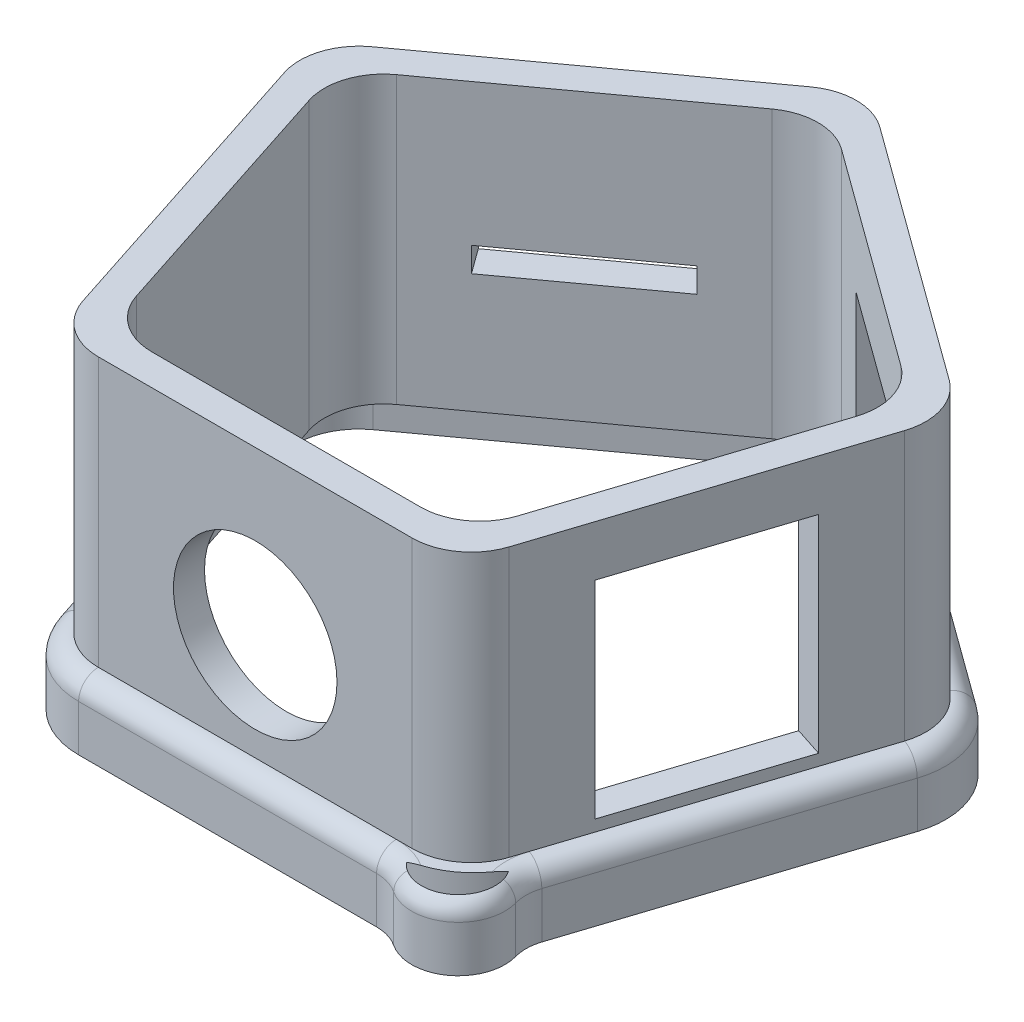
SolidWorks part; units mm, degrees
material "ABS"
ref_plane "Front Plane" through (0, 0, 0) normal (0, 0, 1) x (1, 0, 0)
ref_plane "Top Plane" through (0, 0, 0) normal (0, 1, 0) x (1, 0, 0)
ref_plane "Right Plane" through (0, 0, 0) normal (1, 0, 0) x (0, 0, -1)
sketch "Sketch1" plane through (0, 0, 0) normal (0, 0, 1) x (1, 0, 0)
  line L1 (-22.86, -15.875) -> (22.86, -15.875)
  line L2 (-22.86, -15.875) -> (-22.86, 15.875)
  line L3 (-22.86, 15.875) -> (22.86, 15.875)
  line L4 (22.86, -15.875) -> (22.86, 15.875)
  line L5 (-22.86, -15.875) -> (22.86, 15.875) construction
  line L6 (-22.86, 15.875) -> (22.86, -15.875) construction
  circle A0 centre (0, 0) radius 10.16
  dimension "D1" = 20.32
  dimension "D2" = 45.72
  dimension "D3" = 31.75
extrude "Boss-Extrude1" add sketch "Sketch1" along normal blind 4
sketch "Sketch2" plane through (0, 15.875, 0) normal (0, 1, 0) x (1, 0, 0)
  line L0 (22.86, 0) -> (36.9883, 43.4823)
  line L1 (36.9883, 43.4823) -> (0, 70.3558)
  line L2 (0, 70.3558) -> (-36.9883, 43.4823)
  line L3 (-36.9883, 43.4823) -> (-22.86, 0)
  line L4 (-22.86, 0) -> (22.86, 0)
  line L6 (-41.6905, 45.0102) -> (-25.7662, -4)
  line L7 (-25.7662, -4) -> (25.7662, -4)
  line L8 (25.7662, -4) -> (41.6905, 45.0102)
  line L9 (41.6905, 45.0102) -> (0, 75.3001)
  line L10 (0, 75.3001) -> (-41.6905, 45.0102)
  line L11 (-22.86, 0) -> (-22.86, -4)
  line L12 (-22.86, -4) -> (22.86, 0)
  line L13 (22.86, -4) -> (22.86, 0)
  line M7 (-22.86, 0) -> (-22.86, -4)
  line M9 (22.86, -4) -> (22.86, 0)
  dimension "D1" = 108
  dimension "D2" = 108
  dimension "D3" = 4
extrude "Boss-Extrude2" add sketch "Sketch2" against normal up to surface (31.75 mm away) contours L9 L10 L6 L7 L3 L2 L1 L0 L8 M7 M9 up to face at (0, -15.875, 2)
sketch "Sketch3" plane through (0, 0, 4) normal (0, 0, 1) x (1, 0, 0)
  circle A0 centre (0, 0) radius 10.033
  dimension "D1" = 20.066
extrude "Cut-Extrude1" [suppressed] cut sketch "Sketch3" against normal blind 11.62
sketch "Sketch4" plane through (0, 15.875, 0) normal (0, 1, 0) x (1, 0, 0)
  line L0 (0, 70.3558) -> (0, 0)
  line L1 (22.86, 0) -> (-22.86, 0) construction
  line L2 (36.9883, 43.4823) -> (-29.9241, 21.7412)
  line L3 (-36.9883, 43.4823) -> (-22.86, 0) construction
sketch "Sketch5" plane through (0, 0, 0) normal (1, 0, 0) x (0, 0, -1)
  line L0 (43.4823, 15.875) -> (21.7412, 15.875) construction
  line L1 (43.4823, 15.875) -> (21.7412, 15.875)
  line L2 (31.5133, 15.875) -> (31.5133, 7.2346)
pattern_circular "CirPattern1" [suppressed] count 5 over 360 about axis through (0, 15.875, -31.5133) along (0, -1, 0)
fillet "Fillet1" radius 7.62 10 edges at (-22.86, 0, 0) (-36.9883, 0, -43.4823) (0, 0, -70.3558) (36.9883, 0, -43.4823) (22.86, 0, 0) (25.7662, 0, 4) (41.6905, 0, -45.0102) (0, 0, -75.3001) (-41.6905, 0, -45.0102) (-25.7662, 0, 4)
sketch "Sketch6" plane through (0, 15.875, 0) normal (0, 1, 0) x (1, 0, 0)
  line L0 (24.5708, 5.2653) -> (35.2775, 38.217) construction
  line L1 (17.3237, 0) -> (-17.3237, 0) construction
  line L2 (-35.2775, 38.217) -> (-24.5708, 5.2653) construction
  line L3 (-4.4789, 67.1017) -> (-32.5093, 46.7364) construction
  line L4 (32.5093, 46.7364) -> (4.4789, 67.1017) construction
  line L5 (-20.2299, -4) -> (20.2299, -4)
  line L6 (27.477, 1.2653) -> (39.9797, 39.7449)
  line L7 (37.2116, 48.2643) -> (4.4789, 72.046)
  line L8 (-4.4789, 72.046) -> (-37.2116, 48.2643)
  line L9 (-39.9797, 39.7449) -> (-27.477, 1.2653)
  line L10 (-20.2299, -4) -> (20.2299, -4)
  line L11 (27.477, 1.2653) -> (39.9797, 39.7449)
  line L12 (37.2116, 48.2643) -> (4.4789, 72.046)
  line L13 (-4.4789, 72.046) -> (-37.2116, 48.2643)
  line L14 (-39.9797, 39.7449) -> (-27.477, 1.2653)
  line L15 (24.5708, 5.2653) -> (35.2775, 38.217)
  line L16 (17.3237, 0) -> (-17.3237, 0)
  line L17 (-35.2775, 38.217) -> (-24.5708, 5.2653)
  line L18 (-4.4789, 67.1017) -> (-32.5093, 46.7364)
  line L19 (32.5093, 46.7364) -> (4.4789, 67.1017)
  arc A0 (35.2775, 38.217) -> (32.5093, 46.7364) centre (28.0304, 40.5717) ccw construction
  arc A1 (17.3237, 0) -> (24.5708, 5.2653) centre (17.3237, 7.62) ccw construction
  arc A2 (-24.5708, 5.2653) -> (-17.3237, 0) centre (-17.3237, 7.62) ccw construction
  arc A3 (-32.5093, 46.7364) -> (-35.2775, 38.217) centre (-28.0304, 40.5717) ccw construction
  arc A4 (4.4789, 67.1017) -> (-4.4789, 67.1017) centre (0, 60.937) ccw construction
  arc A5 (20.2299, -4) -> (27.477, 1.2653) centre (20.2299, 3.62) ccw
  arc A6 (39.9797, 39.7449) -> (37.2116, 48.2643) centre (32.7327, 42.0996) ccw
  arc A7 (4.4789, 72.046) -> (-4.4789, 72.046) centre (0, 65.8813) ccw
  arc A8 (-37.2116, 48.2643) -> (-39.9797, 39.7449) centre (-32.7327, 42.0996) ccw
  arc A9 (-27.477, 1.2653) -> (-20.2299, -4) centre (-20.2299, 3.62) ccw
  arc A10 (20.2299, -4) -> (27.477, 1.2653) centre (20.2299, 3.62) ccw
  arc A11 (39.9797, 39.7449) -> (37.2116, 48.2643) centre (32.7327, 42.0996) ccw
  arc A12 (4.4789, 72.046) -> (-4.4789, 72.046) centre (0, 65.8813) ccw
  arc A13 (-37.2116, 48.2643) -> (-39.9797, 39.7449) centre (-32.7327, 42.0996) ccw
  arc A14 (-27.477, 1.2653) -> (-20.2299, -4) centre (-20.2299, 3.62) ccw
  arc A15 (35.2775, 38.217) -> (32.5093, 46.7364) centre (28.0304, 40.5717) ccw
  arc A16 (17.3237, 0) -> (24.5708, 5.2653) centre (17.3237, 7.62) ccw
  arc A17 (-24.5708, 5.2653) -> (-17.3237, 0) centre (-17.3237, 7.62) ccw
  arc A18 (-32.5093, 46.7364) -> (-35.2775, 38.217) centre (-28.0304, 40.5717) ccw
  arc A19 (4.4789, 67.1017) -> (-4.4789, 67.1017) centre (0, 60.937) ccw
  dimension "D1" = 0
extrude "Boss-Extrude3" add sketch "Sketch6" along normal blind 5.08
sketch "Sketch7" plane through (-35.8073, 0, -49.2846) normal (-0.5878, 0, -0.809) x (-0.809, 0, 0.5878)
  line L0 (-18.4941, 20.955) -> (-18.4941, 17.145)
  line L1 (-38.724, 20.955) -> (1.7358, 20.955) construction
  circle A0 centre (-18.4941, 17.145) radius 2.5
  dimension "D1" = 5
  dimension "D2" = 3.81
sketch "Sketch8" plane through (0, -15.875, 0) normal (0, -1, 0) x (1, 0, 0)
  line L0 (-27.477, -1.2653) -> (-39.9797, -39.7449) construction
  line L1 (-27.477, -1.2653) -> (-39.9797, -39.7449)
  line L7 (39.9797, -39.7449) -> (27.477, -1.2653)
  line L8 (20.2299, 4) -> (-20.2299, 4)
  line L9 (-27.477, -1.2653) -> (-39.9797, -39.7449)
  line L10 (-37.2116, -48.2643) -> (-4.4789, -72.046)
  line L11 (4.4789, -72.046) -> (37.2116, -48.2643)
  line L12 (39.9797, -39.7449) -> (27.477, -1.2653)
  line L13 (20.2299, 4) -> (-20.2299, 4)
  line L14 (-27.477, -1.2653) -> (-39.9797, -39.7449)
  line L15 (-37.2116, -48.2643) -> (-4.4789, -72.046)
  line L16 (4.4789, -72.046) -> (37.2116, -48.2643)
  line L22 (42.3954, -38.96) -> (29.8927, -0.4804)
  line L23 (20.2299, 6.54) -> (-20.2299, 6.54)
  line L24 (-29.8927, -0.4804) -> (-42.3954, -38.96)
  line L25 (-38.7046, -50.3192) -> (-5.9719, -74.1009)
  line L26 (5.9719, -74.1009) -> (38.7046, -50.3192)
  line L27 (42.3954, -38.96) -> (29.8927, -0.4804)
  line L28 (20.2299, 6.54) -> (-20.2299, 6.54)
  line L29 (-29.8927, -0.4804) -> (-42.3954, -38.96)
  line L30 (-38.7046, -50.3192) -> (-5.9719, -74.1009)
  line L31 (5.9719, -74.1009) -> (38.7046, -50.3192)
  arc A5 (27.477, -1.2653) -> (20.2299, 4) centre (20.2299, -3.62) ccw
  arc A6 (-20.2299, 4) -> (-27.477, -1.2653) centre (-20.2299, -3.62) ccw
  arc A7 (-39.9797, -39.7449) -> (-37.2116, -48.2643) centre (-32.7327, -42.0996) ccw
  arc A8 (-4.4789, -72.046) -> (4.4789, -72.046) centre (0, -65.8813) ccw
  arc A9 (37.2116, -48.2643) -> (39.9797, -39.7449) centre (32.7327, -42.0996) ccw
  arc A10 (27.477, -1.2653) -> (20.2299, 4) centre (20.2299, -3.62) ccw
  arc A11 (-20.2299, 4) -> (-27.477, -1.2653) centre (-20.2299, -3.62) ccw
  arc A12 (-39.9797, -39.7449) -> (-37.2116, -48.2643) centre (-32.7327, -42.0996) ccw
  arc A13 (-4.4789, -72.046) -> (4.4789, -72.046) centre (0, -65.8813) ccw
  arc A14 (37.2116, -48.2643) -> (39.9797, -39.7449) centre (32.7327, -42.0996) ccw
  arc A20 (29.8927, -0.4804) -> (20.2299, 6.54) centre (20.2299, -3.62) ccw
  arc A21 (-20.2299, 6.54) -> (-29.8927, -0.4804) centre (-20.2299, -3.62) ccw
  arc A22 (-42.3954, -38.96) -> (-38.7046, -50.3192) centre (-32.7327, -42.0996) ccw
  arc A23 (-5.9719, -74.1009) -> (5.9719, -74.1009) centre (0, -65.8813) ccw
  arc A24 (38.7046, -50.3192) -> (42.3954, -38.96) centre (32.7327, -42.0996) ccw
  arc A25 (29.8927, -0.4804) -> (20.2299, 6.54) centre (20.2299, -3.62) ccw
  arc A26 (-20.2299, 6.54) -> (-29.8927, -0.4804) centre (-20.2299, -3.62) ccw
  arc A27 (-42.3954, -38.96) -> (-38.7046, -50.3192) centre (-32.7327, -42.0996) ccw
  arc A28 (-5.9719, -74.1009) -> (5.9719, -74.1009) centre (0, -65.8813) ccw
  arc A29 (38.7046, -50.3192) -> (42.3954, -38.96) centre (32.7327, -42.0996) ccw
  line M31 (39.9797, -39.7449) -> (27.477, -1.2653)
  arc M32 (27.477, -1.2653) -> (20.2299, 4) centre (20.2299, -3.62) ccw
  line M33 (20.2299, 4) -> (-20.2299, 4)
  arc M34 (-20.2299, 4) -> (-27.477, -1.2653) centre (-20.2299, -3.62) ccw
  line M35 (-27.477, -1.2653) -> (-39.9797, -39.7449)
  arc M36 (-39.9797, -39.7449) -> (-37.2116, -48.2643) centre (-32.7327, -42.0996) ccw
  line M37 (-37.2116, -48.2643) -> (-4.4789, -72.046)
  arc M38 (-4.4789, -72.046) -> (4.4789, -72.046) centre (0, -65.8813) ccw
  line M39 (4.4789, -72.046) -> (37.2116, -48.2643)
  arc M40 (37.2116, -48.2643) -> (39.9797, -39.7449) centre (32.7327, -42.0996) ccw
  dimension "D1" = 0
  dimension "D2" = 2.54
extrude "Boss-Extrude4" add sketch "Sketch8" along normal blind 6.35 and the other way blind 2.159 contours L31 A29 L27 A25 L28 A26 L29 A27 L30 A28 M31 M40 M39 M38 M37 M36 M35 M34 M33 M32
sketch "Sketch9" plane through (-37.3003, 0, -51.3395) normal (-0.5878, 0, -0.809) x (-0.809, 0, 0.5878)
  line L0 (1.7358, -15.875) -> (-38.724, -15.875) construction
  line L1 (1.7358, -15.875) -> (-38.724, -15.875)
  line L2 (-18.4941, -15.875) -> (-18.4941, -19.685)
  circle A0 centre (-18.4941, -19.685) radius 1.7
  dimension "D2" = 3.4
  dimension "D1" = 3.81
sketch "Sketch11" plane through (0, -22.225, 0) normal (0, -1, 0) x (1, 0, 0)
  line L0 (20.2299, 6.54) -> (19.9488, 5.4149)
  line L1 (19.9488, 5.4149) -> (27.19, 1.5678)
  line L2 (27.19, 1.5678) -> (29.8927, -0.4804)
  line L5 (5.9719, -74.1009) -> (38.7046, -50.3192)
  line L6 (42.3954, -38.96) -> (29.8927, -0.4804)
  line L7 (20.2299, 6.54) -> (-20.2299, 6.54)
  line L8 (-29.8927, -0.4804) -> (-42.3954, -38.96)
  line L9 (-38.7046, -50.3192) -> (-5.9719, -74.1009)
  line L10 (5.9719, -74.1009) -> (38.7046, -50.3192)
  line L11 (42.3954, -38.96) -> (29.8927, -0.4804)
  line L12 (20.2299, 6.54) -> (-20.2299, 6.54)
  line L13 (-29.8927, -0.4804) -> (-42.3954, -38.96)
  line L14 (-38.7046, -50.3192) -> (-5.9719, -74.1009)
  arc A0 (20.2299, 6.54) -> (29.8927, -0.4804) centre (24.6642, 2.4832) cw
  arc A5 (38.7046, -50.3192) -> (42.3954, -38.96) centre (32.7327, -42.0996) ccw
  arc A6 (29.8927, -0.4804) -> (20.2299, 6.54) centre (20.2299, -3.62) ccw
  arc A7 (-20.2299, 6.54) -> (-29.8927, -0.4804) centre (-20.2299, -3.62) ccw
  arc A8 (-42.3954, -38.96) -> (-38.7046, -50.3192) centre (-32.7327, -42.0996) ccw
  arc A9 (-5.9719, -74.1009) -> (5.9719, -74.1009) centre (0, -65.8813) ccw
  arc A10 (38.7046, -50.3192) -> (42.3954, -38.96) centre (32.7327, -42.0996) ccw
  arc A12 (-20.2299, 6.54) -> (-29.8927, -0.4804) centre (-20.2299, -3.62) ccw
  arc A13 (-42.3954, -38.96) -> (-38.7046, -50.3192) centre (-32.7327, -42.0996) ccw
  arc A14 (-5.9719, -74.1009) -> (5.9719, -74.1009) centre (0, -65.8813) ccw
  arc M24 (29.8927, -0.4804) -> (20.2299, 6.54) centre (20.2299, -3.62) ccw
  dimension "D1" = 0
extrude "Boss-Extrude5" add sketch "Sketch11" against normal up to surface (8.509 mm away) contours L1 L2 L0 M24 | A0 M24 up to face at (0, -13.716, -31.4641)
sketch "Sketch12" plane through (0, -22.225, 0) normal (0, -1, 0) x (1, 0, 0)
  line L0 (20.2299, 6.54) -> (20.2299, 4)
  line L1 (29.8927, -0.4804) -> (27.477, -1.2653)
  line L10 (5.9719, -74.1009) -> (38.7046, -50.3192)
  line L11 (42.3954, -38.96) -> (29.8927, -0.4804)
  line L12 (20.2299, 6.54) -> (-20.2299, 6.54)
  line L13 (-29.8927, -0.4804) -> (-42.3954, -38.96)
  line L14 (-38.7046, -50.3192) -> (-5.9719, -74.1009)
  line L15 (42.3954, -38.96) -> (29.8927, -0.4804)
  line L16 (42.3954, -38.96) -> (29.8927, -0.4804)
  line L17 (20.2299, 6.54) -> (-20.2299, 6.54)
  line L18 (20.2299, 6.54) -> (-20.2299, 6.54)
  line L19 (-29.8927, -0.4804) -> (-42.3954, -38.96)
  line L20 (-29.8927, -0.4804) -> (-42.3954, -38.96)
  line L23 (-38.7046, -50.3192) -> (-5.9719, -74.1009)
  line L24 (-38.7046, -50.3192) -> (-5.9719, -74.1009)
  line L25 (5.9719, -74.1009) -> (38.7046, -50.3192)
  line L26 (5.9719, -74.1009) -> (38.7046, -50.3192)
  arc A0 (27.477, -1.2653) -> (20.2299, 4) centre (20.2299, -3.62) ccw construction
  arc A1 (27.477, -1.2653) -> (20.2299, 4) centre (20.2299, -3.62) ccw
  arc A2 (29.8927, -0.4804) -> (20.2299, 6.54) centre (24.6642, 2.4832) ccw
  arc A4 (29.8927, -0.4804) -> (20.2299, 6.54) centre (24.6642, 2.4832) ccw
  arc A6 (28.7878, 0.1459) -> (21.1669, 5.6827) centre (24.6642, 2.4832) ccw
  arc A7 (21.1669, 5.6827) -> (28.7878, 0.1459) centre (19.5024, -4.6213) cw
  arc A14 (38.7046, -50.3192) -> (42.3954, -38.96) centre (32.7327, -42.0996) ccw
  arc A15 (29.8927, -0.4804) -> (20.2299, 6.54) centre (20.2299, -3.62) ccw
  arc A16 (-20.2299, 6.54) -> (-29.8927, -0.4804) centre (-20.2299, -3.62) ccw
  arc A17 (-42.3954, -38.96) -> (-38.7046, -50.3192) centre (-32.7327, -42.0996) ccw
  arc A18 (-5.9719, -74.1009) -> (5.9719, -74.1009) centre (0, -65.8813) ccw
  arc A22 (-20.2299, 6.54) -> (-29.8927, -0.4804) centre (-20.2299, -3.62) ccw
  arc A23 (-20.2299, 6.54) -> (-29.8927, -0.4804) centre (-20.2299, -3.62) ccw
  arc A24 (-42.3954, -38.96) -> (-38.7046, -50.3192) centre (-32.7327, -42.0996) ccw
  arc A25 (-42.3954, -38.96) -> (-38.7046, -50.3192) centre (-32.7327, -42.0996) ccw
  arc A26 (-5.9719, -74.1009) -> (5.9719, -74.1009) centre (0, -65.8813) ccw
  arc A27 (-5.9719, -74.1009) -> (5.9719, -74.1009) centre (0, -65.8813) ccw
  arc A28 (38.7046, -50.3192) -> (42.3954, -38.96) centre (32.7327, -42.0996) ccw
  arc A29 (38.7046, -50.3192) -> (42.3954, -38.96) centre (32.7327, -42.0996) ccw
  dimension "D1" = 0
  dimension "D3" = 1.27
extrude "Cut-Extrude4" cut sketch "Sketch12" against normal blind 12.192
fillet "Fillet5" radius 5.715 2 edges at (29.8927, -17.9705, -0.4804) (20.2299, -17.9705, 6.54)
fillet "Fillet6" radius 2.54 11 edges at (42.3954, -13.716, -45.2392) (22.3382, -13.716, -62.21) (0, -13.716, -76.0413) (-22.3382, -13.716, -62.21) (-42.3954, -13.716, -45.2392) (-36.144, -13.716, -19.7202) (-26.2018, -13.716, 4.5996) (-1.0228, -13.716, 6.54) (19.8337, -13.716, 6.7832) (30.2464, -13.716, -0.782) (36.4601, -13.716, -20.6929)
sketch "Sketch13" plane through (0, -22.225, 0) normal (0, -1, 0) x (1, 0, 0)
  line L0 (20.2299, 4.6) -> (-20.2299, 4.6)
  line L1 (-28.0476, -1.0799) -> (-40.5504, -39.5595)
  line L2 (-37.5643, -48.7497) -> (-4.8316, -72.5314)
  line L3 (4.8316, -72.5314) -> (37.5643, -48.7497)
  line L4 (40.5504, -39.5595) -> (28.0476, -1.0799)
  line L5 (39.9797, -39.7449) -> (27.477, -1.2653)
  line L6 (4.4789, -72.046) -> (37.2116, -48.2643)
  line L7 (-37.2116, -48.2643) -> (-4.4789, -72.046)
  line L8 (-27.477, -1.2653) -> (-39.9797, -39.7449)
  line L9 (20.2299, 4) -> (-20.2299, 4)
  line L10 (39.9797, -39.7449) -> (27.477, -1.2653)
  line L11 (4.4789, -72.046) -> (37.2116, -48.2643)
  line L12 (-37.2116, -48.2643) -> (-4.4789, -72.046)
  line L13 (-27.477, -1.2653) -> (-39.9797, -39.7449)
  line L14 (20.2299, 4) -> (-20.2299, 4)
  arc A0 (-20.2299, 4.6) -> (-28.0476, -1.0799) centre (-20.2299, -3.62) ccw
  arc A1 (-40.5504, -39.5595) -> (-37.5643, -48.7497) centre (-32.7327, -42.0996) ccw
  arc A2 (28.7878, 0.1459) -> (21.1669, 5.6827) centre (24.6642, 2.4832) ccw
  arc A3 (28.7878, 0.1459) -> (21.1669, 5.6827) centre (19.5024, -4.6213) ccw
  arc A4 (28.7878, 0.1459) -> (21.1669, 5.6827) centre (24.6642, 2.4832) ccw
  arc A5 (37.2116, -48.2643) -> (39.9797, -39.7449) centre (32.7327, -42.0996) ccw
  arc A6 (-4.4789, -72.046) -> (4.4789, -72.046) centre (0, -65.8813) ccw
  arc A7 (-39.9797, -39.7449) -> (-37.2116, -48.2643) centre (-32.7327, -42.0996) ccw
  arc A8 (-20.2299, 4) -> (-27.477, -1.2653) centre (-20.2299, -3.62) ccw
  arc A9 (27.477, -1.2653) -> (20.2299, 4) centre (20.2299, -3.62) ccw
  arc A10 (37.2116, -48.2643) -> (39.9797, -39.7449) centre (32.7327, -42.0996) ccw
  arc A11 (-4.4789, -72.046) -> (4.4789, -72.046) centre (0, -65.8813) ccw
  arc A12 (-39.9797, -39.7449) -> (-37.2116, -48.2643) centre (-32.7327, -42.0996) ccw
  arc A13 (-20.2299, 4) -> (-27.477, -1.2653) centre (-20.2299, -3.62) ccw
  arc A14 (27.477, -1.2653) -> (20.2299, 4) centre (20.2299, -3.62) ccw
  arc A15 (28.7878, 0.1459) -> (21.1669, 5.6827) centre (19.5024, -4.6213) ccw
  arc A16 (-4.8316, -72.5314) -> (4.8316, -72.5314) centre (0, -65.8813) ccw
  arc A17 (37.5643, -48.7497) -> (40.5504, -39.5595) centre (32.7327, -42.0996) ccw
  arc A18 (28.0476, -1.0799) -> (20.2299, 4.6) centre (20.2299, -3.62) ccw
  dimension "D1" = 0
  dimension "D2" = 0
  dimension "D3" = 0.6
extrude "Cut-Extrude5" cut sketch "Sketch13" against normal up to surface (6.35 mm away) up to face at (0, -15.875, -31.4641)
sketch "Sketch14" plane through (24.4813, 0, 7.9545) normal (0.9511, 0, 0.309) x (0.309, 0, -0.9511)
  line L0 (29.9241, 15.875) -> (29.9241, -13.716)
  line L1 (41.3541, -12.2555) -> (18.4941, -12.2555)
  line L2 (41.3541, -12.2555) -> (41.3541, 14.4145)
  line L3 (41.3541, 14.4145) -> (18.4941, 14.4145)
  line L4 (18.4941, -12.2555) -> (18.4941, 14.4145)
  line L5 (41.3541, -12.2555) -> (18.4941, 14.4145) construction
  line L6 (41.3541, 14.4145) -> (18.4941, -12.2555) construction
  line L7 (9.6942, 20.955) -> (9.6942, -13.716) construction
  line L8 (50.154, -13.716) -> (50.154, 20.955) construction
  line L9 (50.154, 15.875) -> (9.6942, 15.875)
  line L10 (9.6942, 20.955) -> (50.154, 20.955) construction
  line L11 (50.154, -13.716) -> (11.7398, -13.716) construction
  point P0 (29.9241, 1.0795)
  point P18 (29.9241, 1.0795)
  dimension "D1" = 22.86
  dimension "D2" = 26.67
  dimension "D3" = 5.08
extrude "Cut-Extrude6" cut sketch "Sketch14" against normal blind 10.16
sketch "Sketch15" plane through (35.8073, 0, -49.2846) normal (0.5878, 0, -0.809) x (-0.809, 0, -0.5878)
  line L0 (38.724, 15.875) -> (-1.7358, 15.875)
  line L1 (18.4941, 15.875) -> (18.4941, -13.716)
  line L2 (27.3841, -8.763) -> (9.6041, -8.763)
  line L3 (27.3841, -8.763) -> (27.3841, 10.922)
  line L4 (-1.7358, 20.955) -> (-1.7358, -13.716)
  line L5 (-1.7358, -13.716) -> (38.724, -13.716)
  line L7 (-1.7358, 20.955) -> (-1.7358, -13.716)
  line L9 (-1.7358, -13.716) -> (38.724, -13.716)
  line L12 (27.3841, 10.922) -> (9.6041, 10.922)
  line L13 (9.6041, -8.763) -> (9.6041, 10.922)
  line L14 (27.3841, -8.763) -> (9.6041, 10.922) construction
  line L15 (27.3841, 10.922) -> (9.6041, -8.763) construction
  line L20 (38.724, -13.716) -> (38.724, 20.955)
  line L22 (38.724, -13.716) -> (38.724, 20.955)
  line L23 (38.724, 20.955) -> (-1.7358, 20.955)
  line L24 (38.724, 20.955) -> (-1.7358, 20.955)
  point P6 (18.4941, 1.0795)
  point P13 (18.4941, 1.0795)
  dimension "D2" = 19.685
  dimension "D3" = 17.78
  dimension "D4" = 5.08
  dimension "D1" = 0
extrude "Cut-Extrude7" cut sketch "Sketch15" against normal blind 10.16
sketch "Sketch16" plane through (-35.8073, 0, -49.2846) normal (-0.5878, 0, -0.809) x (-0.809, 0, 0.5878)
  line L0 (1.7358, 15.875) -> (-38.724, 15.875)
  line L1 (-18.4941, -13.716) -> (-18.4941, 15.875)
  line L2 (-28.9081, -0.508) -> (-8.0801, -0.508)
  line L3 (-28.9081, -0.508) -> (-28.9081, 2.667)
  line L4 (-38.724, 20.955) -> (-38.724, -13.716)
  line L5 (-38.724, -13.716) -> (1.7358, -13.716)
  line L7 (-38.724, 20.955) -> (-38.724, -13.716)
  line L9 (-38.724, -13.716) -> (1.7358, -13.716)
  line L12 (-28.9081, 2.667) -> (-8.0801, 2.667)
  line L13 (-8.0801, -0.508) -> (-8.0801, 2.667)
  line L14 (-28.9081, -0.508) -> (-8.0801, 2.667) construction
  line L15 (-28.9081, 2.667) -> (-8.0801, -0.508) construction
  line L20 (1.7358, -13.716) -> (1.7358, 20.955)
  line L22 (1.7358, -13.716) -> (1.7358, 20.955)
  line L23 (1.7358, 20.955) -> (-38.724, 20.955)
  line L24 (1.7358, 20.955) -> (-38.724, 20.955)
  point P6 (-18.4941, 1.0795)
  point P13 (-18.4941, 1.0795)
  dimension "D2" = 20.828
  dimension "D3" = 3.175
  dimension "D4" = 5.08
  dimension "D1" = 0
extrude "Cut-Extrude8" cut sketch "Sketch16" against normal blind 10.16
sketch "Sketch17" plane through (0, 0, 4) normal (0, 0, 1) x (1, 0, 0)
  circle A0 centre (0, 0) radius 10.16 construction
  circle A1 centre (0, 0) radius 10.16
  circle A2 centre (0, 0) radius 10.541
  dimension "D1" = 21.082
extrude "Cut-Extrude9" cut sketch "Sketch17" against normal blind 9.398
